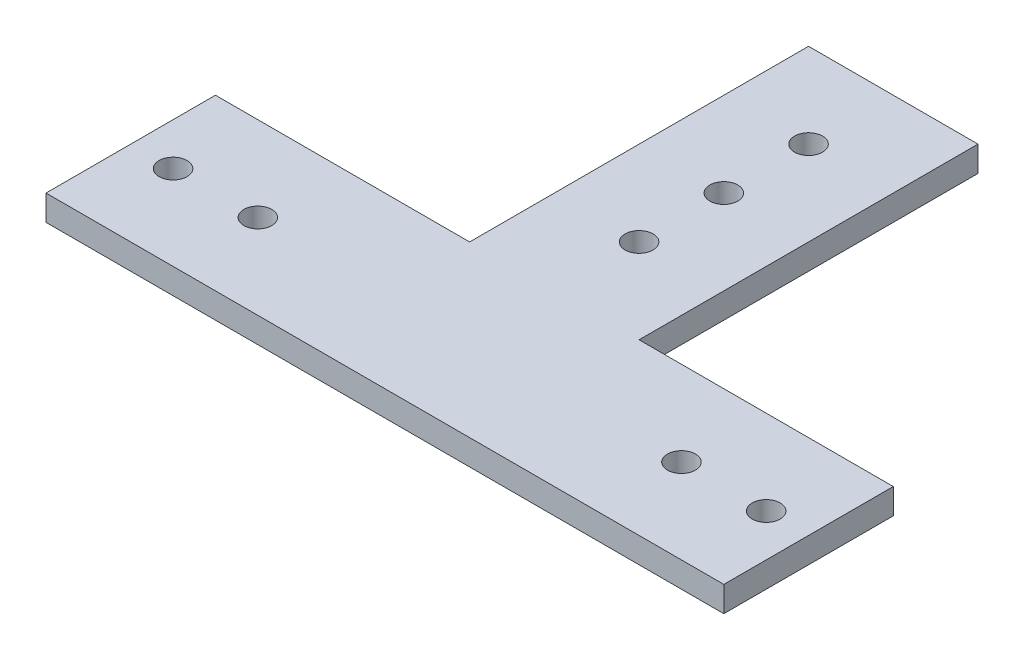
SolidWorks part; units mm, degrees
ref_plane "前视基准面" through (0, 0, 0) normal (0, 0, 1) x (1, 0, 0)
ref_plane "上视基准面" through (0, 0, 0) normal (0, 1, 0) x (1, 0, 0)
ref_plane "右视基准面" through (0, 0, 0) normal (1, 0, 0) x (0, 0, -1)
other "Configuration Table"
sketch "草图1" plane through (0, 0, 0) normal (0, 1, 0) x (1, 0, 0)
  line L0 (-40.3341, -30.3341) -> (39.6659, -30.3341)
  line L1 (39.6659, -30.3341) -> (39.6659, -10.3341)
  line L2 (39.6659, -10.3341) -> (9.6659, -10.3341)
  line L3 (9.6659, -10.3341) -> (9.6659, 29.6659)
  line L4 (9.6659, 29.6659) -> (-10.3341, 29.6659)
  line L5 (-10.3341, 29.6659) -> (-10.3341, -10.3341)
  line L6 (-10.3341, -10.3341) -> (-40.3341, -10.3341)
  line L7 (-40.3341, -10.3341) -> (-40.3341, -30.3341)
  circle A0 centre (-0.3341, -0.3341) radius 1.65
  circle A1 centre (-0.3341, 9.6659) radius 1.65
  circle A2 centre (-0.3341, 19.6659) radius 1.65
  circle A3 centre (-25.3341, -20.3341) radius 1.65
  circle A4 centre (-35.3341, -20.3341) radius 1.65
  circle A5 centre (24.6659, -20.3341) radius 1.65
  circle A6 centre (34.6659, -20.3341) radius 1.65
  dimension "D1" = 3.3
extrude "凸台-拉伸1" add sketch "草图1" along normal blind 3
